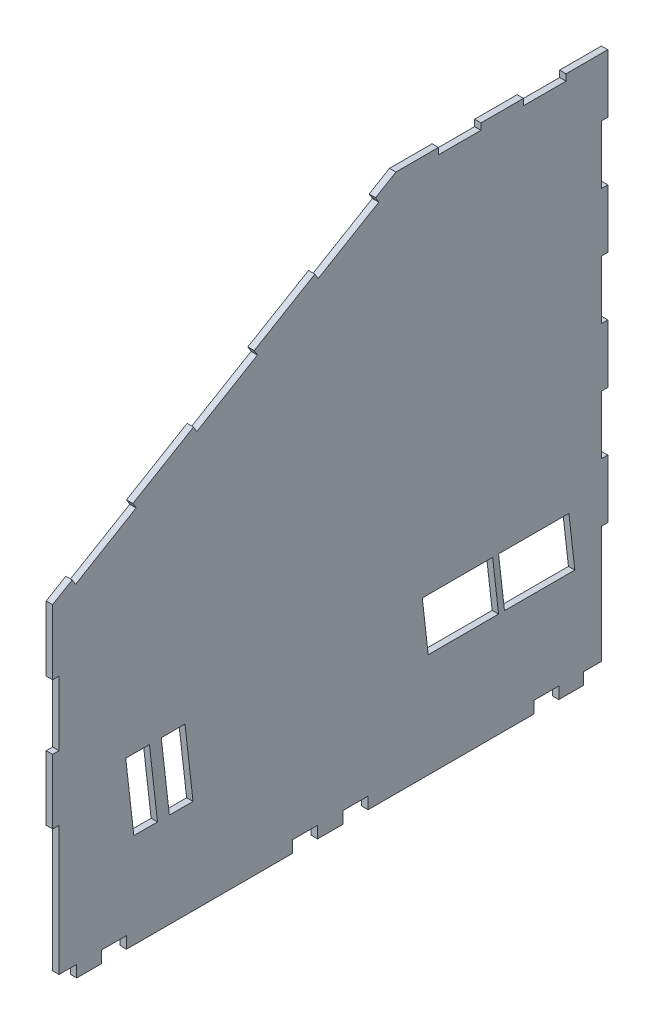
SolidWorks part; units mm, degrees
ref_plane "Ön Düzlem" through (0, 0, 0) normal (0, 0, 1) x (1, 0, 0)
ref_plane "Üst Düzlem" through (0, 0, 0) normal (0, 1, 0) x (1, 0, 0)
ref_plane "Sağ Düzlem" through (0, 0, 0) normal (1, 0, 0) x (0, 0, -1)
sketch "Sketch1" plane through (0, 0, 0) normal (1, 0, 0) x (0, 0, -1)
  line L0 (117.19, 112.5) -> (99.566, 112.5)
  line L13 (-107.0133, -112.5) -> (-107.0133, -114.8)
  line L14 (-6.4686, 92.2661) -> (-32.0795, 77.122)
  line L17 (27.75, 112.5) -> (19.1423, 107.4101)
  line L18 (-114.49, -109.8) -> (-107.0133, -109.8)
  line L20 (-107.0133, -114.8) -> (-96.5067, -114.8)
  line L21 (-86, -112.5) -> (-86, -114.8)
  line L24 (-96.5067, -114.8) -> (-96.5067, -112.5)
  line L26 (-117.19, -0.68) -> (-114.82, -0.68)
  line L27 (-117.19, -27.96) -> (-114.82, -27.96)
  line L29 (-117.19, -55.24) -> (-114.82, -55.24)
  line L31 (-86, -109.8) -> (-86, -112.5)
  line L32 (-107.0133, -109.8) -> (-107.0133, -112.5)
  line L33 (-96.5067, -109.8) -> (-96.5067, -112.5)
  line L34 (-96.5067, -109.8) -> (-86, -109.8)
  line L35 (-5.3333, -112.5) -> (-5.3333, -114.8)
  line L37 (-16, -112.5) -> (-16, -109.8)
  line L38 (-16, -109.8) -> (-5.3333, -109.8)
  line L39 (-5.3333, -114.8) -> (5.3333, -114.8)
  line L40 (-86, -114.8) -> (-16, -114.8)
  line L41 (5.3333, -109.8) -> (16, -109.8)
  line L42 (-5.3333, -109.8) -> (-5.3333, -112.5)
  line L43 (5.3333, -109.8) -> (5.3333, -112.5)
  line L44 (16, -109.8) -> (16, -112.5)
  line L45 (5.3333, -114.8) -> (5.3333, -112.5)
  line L46 (96.5067, -112.5) -> (96.5067, -114.8)
  line L48 (86, -109.8) -> (96.5067, -109.8)
  line L49 (96.5067, -114.8) -> (107.0133, -114.8)
  line L51 (86, -109.8) -> (86, -112.5)
  line L52 (96.5067, -109.8) -> (96.5067, -112.5)
  line L53 (107.0133, -109.8) -> (107.0133, -112.5)
  line L55 (107.0133, -109.8) -> (114.49, -109.8)
  line L61 (107.0133, -112.5) -> (107.0133, -114.8)
  line L65 (117.19, 13.7) -> (114.82, 13.7)
  line L66 (117.19, 87.8) -> (114.82, 87.8)
  line L67 (117.19, 63.1) -> (114.82, 63.1)
  line L68 (117.19, 38.4) -> (114.82, 38.4)
  line L69 (117.19, -11) -> (114.82, -11)
  line L70 (117.19, -35.7) -> (114.82, -35.7)
  line L71 (117.19, -60.4) -> (114.82, -60.4)
  line L72 (-57.6905, 61.978) -> (-83.3014, 46.8339)
  line L73 (-5.0944, 89.942) -> (-6.4686, 92.2661)
  line L74 (-107.538, 29.3658) -> (-81.9271, 44.5098)
  line L75 (-16, -114.8) -> (-16, -112.5)
  line L76 (99.566, 109.8) -> (81.612, 109.8)
  line L77 (16, -112.5) -> (16, -114.8)
  line L78 (63.658, 109.8) -> (45.704, 109.8)
  line L79 (-108.9123, 31.6899) -> (-117.19, 26.7951)
  line L80 (45.704, 109.8) -> (45.704, 112.5)
  line L81 (63.658, 109.8) -> (63.658, 112.5)
  line L82 (81.612, 109.8) -> (81.612, 112.5)
  line L83 (99.566, 109.8) -> (99.566, 112.5)
  line L84 (16, -114.8) -> (86, -114.8)
  line L85 (86, -114.8) -> (86, -112.5)
  line L87 (-108.9123, 31.6899) -> (-107.538, 29.3658)
  line L88 (19.1423, 107.4101) -> (20.5165, 105.086)
  line L89 (-56.3162, 59.6539) -> (-30.7053, 74.7979)
  line L91 (-5.0944, 89.942) -> (20.5165, 105.086)
  line L92 (-30.7053, 74.7979) -> (-32.0795, 77.122)
  line L93 (-56.3162, 59.6539) -> (-57.6905, 61.978)
  line L94 (-81.9271, 44.5098) -> (-83.3014, 46.8339)
  line L95 (45.704, 112.5) -> (27.75, 112.5)
  line L97 (81.612, 112.5) -> (63.658, 112.5)
  line L209 (100.78, -48.8) -> (71.08, -48.8)
  line L211 (100.78, -70.8) -> (73.58, -70.8)
  line L212 (68.58, -48.8) -> (71.08, -70.8)
  line L215 (71.08, -48.8) -> (73.58, -70.8)
  line L216 (41.38, -48.8) -> (38.88, -48.8)
  line L217 (38.88, -48.8) -> (41.38, -70.8)
  line L218 (100.78, -70.8) -> (103.28, -70.8)
  line L219 (100.78, -48.8) -> (103.28, -70.8)
  line L220 (71.08, -70.8) -> (41.38, -70.8)
  line L221 (68.58, -48.8) -> (41.38, -48.8)
  line L226 (-72.9109, -74.8) -> (-76.32, -44.8)
  line L227 (-67.9109, -74.8) -> (-71.32, -44.8)
  line L233 (-82.9109, -74.8) -> (-86.32, -44.8)
  line L235 (-57.9109, -74.8) -> (-61.32, -44.8)
  line L238 (-62.9109, -74.8) -> (-66.32, -44.8) [skipped]
  line L239 (-76.32, -44.8) -> (-86.32, -44.8)
  line L240 (-82.9109, -74.8) -> (-72.9109, -74.8)
  line L241 (-67.9109, -74.8) -> (-57.9109, -74.8)
  line L242 (-71.32, -44.8) -> (-61.32, -44.8)
  line L244 (114.82, 87.8) -> (114.49, 87.8)
  line L245 (-114.82, -0.68) -> (-114.49, -0.68)
  line L246 (117.19, -60.4) -> (117.19, -35.7)
  line L247 (114.49, -109.8) -> (114.49, -60.4)
  line L248 (114.82, 63.1) -> (114.49, 63.1)
  line L249 (114.82, 38.4) -> (114.49, 38.4)
  line L250 (114.82, 13.7) -> (114.49, 13.7)
  line L251 (114.82, -11) -> (114.49, -11)
  line L252 (114.82, -35.7) -> (114.49, -35.7)
  line L253 (114.82, -60.4) -> (114.49, -60.4)
  line L254 (117.19, 87.8) -> (117.19, 112.5)
  line L255 (114.49, 63.1) -> (114.49, 87.8)
  line L256 (117.19, 38.4) -> (117.19, 63.1)
  line L257 (117.19, -11) -> (117.19, 13.7)
  line L258 (114.49, -35.7) -> (114.49, -11)
  line L259 (114.49, 13.7) -> (114.49, 38.4)
  line L260 (-117.19, -0.68) -> (-117.19, 26.7951)
  line L261 (-114.49, -109.8) -> (-114.49, -55.24)
  line L262 (-117.19, -55.24) -> (-117.19, -27.96)
  line L263 (-114.82, -27.96) -> (-114.49, -27.96)
  line L264 (-114.82, -55.24) -> (-114.49, -55.24)
  line L265 (-114.49, -27.96) -> (-114.49, -0.68)
  point P0 (0, 0)
  dimension "D1" = 3
extrude "Boss-Extrude1" add sketch "Sketch1" along normal blind 2.7 contours L82 L97 L81 L78 L80 L95 L17 L88 L91 L73 L14 L92 L89 L93 L72 L94 L74 L87 L79 L26 L27 L29 L18 L32 L33 L34 L31 L37 L38 L42 L43 L41 L44 L51 L48 L52 L53 region at (0, -10.0395, -8.3902)
ref_plane "Plane1" through (2.7, 112.5, -27.75) normal (0, -0.509, 0.8608) x (1, 0, 0)
